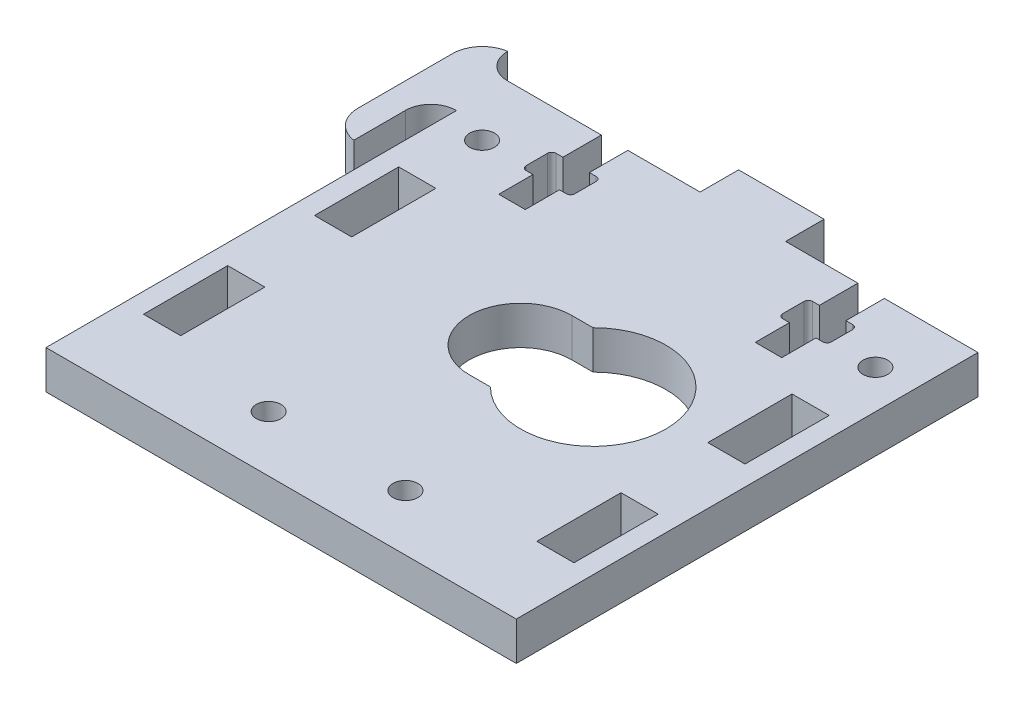
SolidWorks part; units mm, degrees
ref_plane "Front Plane" through (0, 0, 0) normal (0, 0, 1) x (1, 0, 0)
ref_plane "Top Plane" through (0, 0, 0) normal (0, 1, 0) x (1, 0, 0)
ref_plane "Right Plane" through (0, 0, 0) normal (1, 0, 0) x (0, 0, -1)
sketch "Sketch1" plane through (0, 0, 0) normal (0, 1, 0) x (1, 0, 0)
  line L1 (-27.5, 27) -> (27.5, 27)
  line L2 (-27.5, 27) -> (-27.5, -27)
  line L3 (-27.5, -27) -> (27.5, -27)
  line L4 (27.5, 27) -> (27.5, -27)
  line L5 (-27.5, 27) -> (27.5, -27) construction
  line L6 (-27.5, -27) -> (27.5, 27) construction
  point P0 (0, 0)
  dimension "D1" = 55
  dimension "D2" = 54
extrude "MainShape" add sketch "Sketch1" along normal blind 4.5
sketch "Sketch2" plane through (0, 4.5, 0) normal (0, 1, 0) x (1, 0, 0)
  line L0 (0, -27) -> (0, 27) construction
  line L1 (-27.5, -27) -> (27.5, -27) construction
  line L2 (27.5, 27) -> (-27.5, 27) construction
  line L4 (-5, 31.5) -> (5, 31.5)
  line L5 (-5, 31.5) -> (-5, 22.5)
  line L6 (-5, 22.5) -> (5, 22.5)
  line L7 (5, 31.5) -> (5, 22.5)
  line L8 (-5, 31.5) -> (5, 22.5) construction
  line L9 (-5, 22.5) -> (5, 31.5) construction
  dimension "D1" = 10
  dimension "D2" = 4.5
extrude "Tab1" add sketch "Sketch2" against normal through all
sketch "Sketch4" plane through (0, 4.5, 0) normal (0, 1, 0) x (1, 0, 0)
  line L0 (0, 31.5) -> (0, -27) construction
  line L1 (5, 31.5) -> (-5, 31.5) construction
  line L2 (-27.5, -27) -> (27.5, -27) construction
  line L3 (-15, 27) -> (-15, 15) construction
  line L4 (-5, 27) -> (-27.5, 27) construction
  line L5 (-13.45, 15) -> (-16.55, 15) construction
  line L6 (-16.55, 15) -> (-16.55, 27) construction
  line L7 (-13.45, 15) -> (-16.55, 15)
  line L8 (-16.55, 15) -> (-16.55, 19)
  line L9 (-16.55, 19) -> (-17.35, 19)
  line L10 (-17.85, 19.5) -> (-17.85, 22)
  line L11 (-17.35, 22.5) -> (-16.55, 22.5)
  line L12 (-16.55, 22.5) -> (-16.55, 27)
  line L13 (-16.55, 27) -> (-13.45, 27)
  line L14 (-13.45, 15) -> (-13.45, 27) construction
  line L15 (-13.45, 22.5) -> (-13.45, 27)
  line L16 (-12.65, 22.5) -> (-13.45, 22.5)
  line L17 (-12.15, 19.5) -> (-12.15, 22)
  line L18 (-13.45, 19) -> (-12.65, 19)
  line L19 (-13.45, 15) -> (-13.45, 19)
  line L20 (13.45, 15) -> (13.45, 27) construction
  line L21 (16.55, 15) -> (16.55, 27) construction
  line L22 (13.45, 15) -> (16.55, 15) construction
  line L23 (15, 27) -> (15, 15) construction
  line L24 (13.45, 15) -> (13.45, 19)
  line L25 (13.45, 19) -> (12.65, 19)
  line L26 (12.15, 19.5) -> (12.15, 22)
  line L27 (12.65, 22.5) -> (13.45, 22.5)
  line L28 (13.45, 22.5) -> (13.45, 27)
  line L29 (16.55, 27) -> (13.45, 27)
  line L30 (16.55, 22.5) -> (16.55, 27)
  line L31 (17.35, 22.5) -> (16.55, 22.5)
  line L32 (17.85, 19.5) -> (17.85, 22)
  line L33 (16.55, 19) -> (17.35, 19)
  line L34 (16.55, 15) -> (16.55, 19)
  line L35 (13.45, 15) -> (16.55, 15)
  arc A0 (-17.35, 19) -> (-17.85, 19.5) centre (-17.35, 19.5) cw
  arc A1 (-12.15, 19.5) -> (-12.65, 19) centre (-12.65, 19.5) cw
  arc A2 (-12.65, 22.5) -> (-12.15, 22) centre (-12.65, 22) cw
  arc A3 (-17.85, 22) -> (-17.35, 22.5) centre (-17.35, 22) cw
  arc A4 (17.85, 22) -> (17.35, 22.5) centre (17.35, 22) ccw
  arc A5 (12.65, 22.5) -> (12.15, 22) centre (12.65, 22) ccw
  arc A6 (12.15, 19.5) -> (12.65, 19) centre (12.65, 19.5) ccw
  arc A7 (17.35, 19) -> (17.85, 19.5) centre (17.35, 19.5) ccw
  point P24 (-17.85, 19)
  point P27 (-12.15, 19)
  point P30 (-12.15, 22.5)
  point P33 (-17.85, 22.5)
  point P56 (17.85, 22.5)
  point P57 (12.15, 22.5)
  point P58 (12.15, 19)
  point P59 (17.85, 19)
  dimension "D7" = 0.5
  dimension "D1" = 12
  dimension "D2" = 1.55
  dimension "D3" = 3.5
  dimension "D4" = 2.85
  dimension "D5" = 8
  dimension "D6" = 15
extrude "Cut-Extrude2" cut sketch "Sketch4" against normal through all
sketch "Sketch5" plane through (0, 4.5, 0) normal (0, 1, 0) x (1, 0, 0)
  line L0 (0, -27) -> (0, 31.5) construction
  line L1 (-27.5, -27) -> (27.5, -27) construction
  line L2 (5, 31.5) -> (-5, 31.5) construction
  line L3 (23, 27) -> (23, -27) construction
  line L4 (27.5, 27) -> (16.55, 27) construction
  line L5 (-23, 27) -> (-23, -27) construction
  line L6 (20.825, 11.925) -> (25.175, 11.925)
  line L7 (20.825, 11.925) -> (20.825, 2.075)
  line L8 (20.825, 2.075) -> (25.175, 2.075)
  line L9 (25.175, 11.925) -> (25.175, 2.075)
  line L10 (20.825, 11.925) -> (25.175, 2.075) construction
  line L11 (20.825, 2.075) -> (25.175, 11.925) construction
  line L12 (-20.825, 2.075) -> (-25.175, 11.925) construction
  line L13 (-20.825, 11.925) -> (-25.175, 2.075) construction
  line L14 (-25.175, 11.925) -> (-25.175, 2.075)
  line L15 (-20.825, 2.075) -> (-25.175, 2.075)
  line L16 (-20.825, 11.925) -> (-20.825, 2.075)
  line L17 (-20.825, 11.925) -> (-25.175, 11.925)
  line L18 (-27.5, -3) -> (27.5, -3) construction
  line L19 (-27.5, 27) -> (-27.5, -27) construction
  line L20 (27.5, -27) -> (27.5, 27) construction
  line L21 (-20.825, -17.925) -> (-25.175, -8.075) construction
  line L22 (-20.825, -8.075) -> (-25.175, -17.925) construction
  line L23 (20.825, -8.075) -> (25.175, -17.925) construction
  line L24 (20.825, -17.925) -> (25.175, -8.075) construction
  line L25 (-20.825, -17.925) -> (-25.175, -17.925)
  line L26 (-20.825, -17.925) -> (-20.825, -8.075)
  line L27 (-20.825, -8.075) -> (-25.175, -8.075)
  line L28 (-25.175, -17.925) -> (-25.175, -8.075)
  line L29 (25.175, -17.925) -> (25.175, -8.075)
  line L30 (20.825, -8.075) -> (25.175, -8.075)
  line L31 (20.825, -17.925) -> (20.825, -8.075)
  line L32 (20.825, -17.925) -> (25.175, -17.925)
  line L33 (-20.825, 11.925) -> (-25.175, 2.075) construction
  point P10 (23, 7)
  point P21 (-23, 7)
  point P36 (-23, -13)
  point P37 (23, -13)
  dimension "D1" = 23
  dimension "D2" = 9.85
  dimension "D3" = 4.35
  dimension "D4" = 20
  dimension "D5" = 20
extrude "Cut-Extrude3" cut sketch "Sketch5" against normal through all
sketch "Sketch6" plane through (0, 4.5, 0) normal (0, 1, 0) x (1, 0, 0)
  line L0 (0, -27) -> (0, 27) construction
  line L1 (5, 31.5) -> (-5, 31.5) construction
  line L3 (-27.5, 1) -> (27.5, 1) construction
  line L4 (-27.5, 27) -> (-27.5, -27) construction
  line L5 (27.5, -27) -> (27.5, 27) construction
  line L6 (27.5, 27) -> (16.55, 27) construction
  line L7 (-27.5, -27) -> (27.5, -27) construction
  line L9 (-27.5, 27) -> (27.5, 27) construction
  circle A0 centre (0, 1) radius 12
  point P4 (0, 31.5)
  dimension "D1" = 24
  dimension "D2" = 26
extrude "Cut-Extrude4" cut sketch "Sketch6" against normal through all
sketch "Sketch7" plane through (0, 4.5, 0) normal (0, 1, 0) x (1, 0, 0)
  line L0 (0, 1) -> (0, -27) construction
  line L3 (-27.5, -27) -> (27.5, -27) construction
  line L4 (8, -20.46) -> (-8, -20.46) construction
  circle A1 centre (-8, -20.46) radius 1.45
  circle A2 centre (8, -20.46) radius 1.45
  point P8 (0, -20.46)
  dimension "D1" = 2.9
  dimension "D3" = 21.46
extrude "Cut-Extrude5" [suppressed] cut sketch "Sketch7" against normal through all
sketch "Sketch8" plane through (0, 4.5, 0) normal (0, 1, 0) x (1, 0, 0)
  line L0 (-12, 1) -> (12, 1) construction
  line L1 (0, 1) -> (0, -20.46) construction
  line L2 (8, -20.46) -> (-8, -20.46) construction
  line L3 (0, -11) -> (0, 13) construction
  circle A0 centre (-8, -20.46) radius 1.45
  circle A1 centre (0, 1) radius 12 construction
  circle A2 centre (8, -20.46) radius 1.45
  dimension "D3" = 2.9
  dimension "D1" = 90
  dimension "D4" = 21.46
extrude "Cut-Extrude6" cut sketch "Sketch8" against normal through all
sketch "Sketch9" plane through (0, 4.5, 0) normal (0, 1, 0) x (1, 0, 0)
  line L0 (0, -27) -> (0, 31.5) construction
  line L1 (-27.5, -27) -> (27.5, -27) construction
  line L2 (5, 31.5) -> (-5, 31.5) construction
  line L3 (16, -27) -> (16, -16) construction
  line L4 (14.45, -16) -> (17.55, -16) construction
  line L5 (17.55, -16) -> (17.55, -27) construction
  line L6 (17.55, -27) -> (17.55, -22.5)
  line L7 (17.55, -22.5) -> (18.35, -22.5)
  line L8 (18.85, -22) -> (18.85, -19.5)
  line L9 (18.35, -19) -> (17.55, -19)
  line L10 (17.55, -19) -> (17.55, -16)
  line L11 (17.55, -16) -> (14.45, -16)
  line L12 (17.55, -27) -> (14.45, -27)
  line L13 (14.45, -16) -> (14.45, -27) construction
  line L14 (14.45, -19) -> (14.45, -16)
  line L15 (13.65, -19) -> (14.45, -19)
  line L16 (13.15, -22) -> (13.15, -19.5)
  line L17 (14.45, -22.5) -> (13.65, -22.5)
  line L18 (14.45, -27) -> (14.45, -22.5)
  line L19 (-14.45, -16) -> (-14.45, -27) construction
  line L20 (-17.55, -16) -> (-17.55, -27) construction
  line L21 (-14.45, -16) -> (-17.55, -16) construction
  line L22 (-16, -27) -> (-16, -16) construction
  line L23 (-14.45, -27) -> (-14.45, -22.5)
  line L24 (-14.45, -22.5) -> (-13.65, -22.5)
  line L25 (-13.15, -22) -> (-13.15, -19.5)
  line L26 (-13.65, -19) -> (-14.45, -19)
  line L27 (-14.45, -19) -> (-14.45, -16)
  line L28 (-17.55, -27) -> (-14.45, -27)
  line L29 (-17.55, -16) -> (-14.45, -16)
  line L30 (-17.55, -19) -> (-17.55, -16)
  line L31 (-18.35, -19) -> (-17.55, -19)
  line L32 (-18.85, -22) -> (-18.85, -19.5)
  line L33 (-17.55, -22.5) -> (-18.35, -22.5)
  line L34 (-17.55, -27) -> (-17.55, -22.5)
  arc A0 (18.35, -22.5) -> (18.85, -22) centre (18.35, -22) ccw
  arc A1 (18.85, -19.5) -> (18.35, -19) centre (18.35, -19.5) ccw
  arc A2 (13.15, -19.5) -> (13.65, -19) centre (13.65, -19.5) cw
  arc A3 (13.65, -22.5) -> (13.15, -22) centre (13.65, -22) cw
  arc A4 (-13.65, -22.5) -> (-13.15, -22) centre (-13.65, -22) ccw
  arc A5 (-13.15, -19.5) -> (-13.65, -19) centre (-13.65, -19.5) ccw
  arc A6 (-18.85, -19.5) -> (-18.35, -19) centre (-18.35, -19.5) cw
  arc A7 (-18.35, -22.5) -> (-18.85, -22) centre (-18.35, -22) cw
  point P16 (18.85, -22.5)
  point P19 (18.85, -19)
  point P30 (13.15, -19)
  point P31 (13.15, -22.5)
  point P54 (-13.15, -22.5)
  point P55 (-13.15, -19)
  point P56 (-18.85, -19)
  point P57 (-18.85, -22.5)
  dimension "D7" = 0.5
  dimension "D2" = 1.55
  dimension "D1" = 11
  dimension "D3" = 8
  dimension "D4" = 3.5
  dimension "D5" = 2.85
  dimension "D6" = 16
extrude "Cut-Extrude7" [suppressed] cut sketch "Sketch9" against normal through all
sketch "Sketch10" [suppressed] plane through (0, 0, 27) normal (0, 0, 1) x (1, 0, 0)
  line L0 (-27.5, 2.25) -> (27.5, 2.25) construction
  line L1 (-27.5, 4.5) -> (-27.5, 0) construction
  line L2 (27.5, 4.5) -> (27.5, 0) construction
  line L3 (-16, 4.5) -> (-16, 0) construction
  line L4 (-14.25, 4.5) -> (-17.75, 4.5) construction
  line L5 (16, 4.5) -> (16, 0) construction
  line L6 (17.75, 4.5) -> (14.25, 4.5) construction
  line L7 (17.75, 0) -> (14.25, 0) construction
  line L8 (-14.25, 0) -> (-17.75, 0) construction
  circle A0 centre (-16, 2.25) radius 1.6
  circle A1 centre (16, 2.25) radius 1.6
  dimension "D1" = 3.2
  dimension "D2" = 3.2
sketch "Sketch11" plane through (0, 4.5, 0) normal (0, 1, 0) x (1, 0, 0)
  line L0 (-20.825, 7) -> (-25.175, 7) construction
  line L1 (-20.825, 2.075) -> (-20.825, 11.925) construction
  line L2 (-25.175, 11.925) -> (-25.175, 2.075) construction
  line L3 (-23, 7) -> (-23, 27) construction
  line L4 (-16.55, 27) -> (-27.5, 27) construction
  line L5 (0, 31.5) -> (0, 0) construction
  line L6 (5, 31.5) -> (-5, 31.5) construction
  line L7 (23, 7) -> (23, 27) construction
  line L8 (20.825, 7) -> (25.175, 7) construction
  line L9 (-23, 7) -> (-23, 27) construction
  circle A0 centre (-23, 19.5) radius 1.45
  circle A1 centre (23, 19.5) radius 1.45
  dimension "D1" = 2.9
  dimension "D2" = 7.5
extrude "Cut-Extrude8" cut sketch "Sketch11" against normal through all
sketch "Sketch12" [suppressed] plane through (0, 4.5, 0) normal (0, 1, 0) x (1, 0, 0)
  line L0 (-27.5, -7) -> (-34, -17)
  line L1 (-27.5, 27) -> (-27.5, -27) construction
  line L2 (-34, -17) -> (-34, -27)
  line L3 (-34, -27) -> (-27.5, -27)
  line L4 (-27.5, -27) -> (-27.5, -7)
  line L5 (-27.5, -27) -> (27.5, -27) construction
  line L6 (0, -27) -> (0, 31.5) construction
  line L7 (5, 31.5) -> (-5, 31.5) construction
  line L8 (27.5, -27) -> (27.5, -7)
  line L9 (34, -27) -> (27.5, -27)
  line L10 (34, -17) -> (34, -27)
  line L11 (27.5, -7) -> (34, -17)
  point P4 (0, -27)
  dimension "D1" = 34
  dimension "D2" = 10
  dimension "D3" = 20
extrude "Boss-Extrude1" [suppressed] add sketch "Sketch12" against normal through all
sketch "Sketch14" [suppressed] plane through (0, 4.5, 0) normal (0, 1, 0) x (1, 0, 0)
  line L0 (-34, -27) -> (34, -27) construction
  line L2 (-34, -27) -> (34, -27) construction
  line L3 (0, -27) -> (0, 31.5) construction
  line L4 (5, 31.5) -> (-5, 31.5) construction
  line L6 (26.25, -16.5) -> (26.25, -27) construction
  line L8 (-28, -27) -> (-28, -16.5) construction
  line L9 (-26.25, -16.5) -> (-29.75, -16.5) construction
  line L10 (-29.75, -16.5) -> (-29.75, -27) construction
  line L11 (-26.25, -27) -> (-29.75, -27)
  line L12 (-29.75, -27) -> (-29.75, -23.2)
  line L13 (-29.75, -23.2) -> (-30.75, -23.2)
  line L14 (-31, -22.95) -> (-31, -19.25)
  line L15 (-30.75, -19) -> (-29.75, -19)
  line L16 (-29.75, -19) -> (-29.75, -16.5)
  line L17 (-29.75, -16.5) -> (-26.25, -16.5)
  line L18 (-26.25, -16.5) -> (-26.25, -27) construction
  line L19 (-26.25, -19) -> (-26.25, -16.5)
  line L20 (-25.25, -19) -> (-26.25, -19)
  line L21 (-25, -22.95) -> (-25, -19.25)
  line L22 (-26.25, -23.2) -> (-25.25, -23.2)
  line L23 (-26.25, -27) -> (-26.25, -23.2)
  line L24 (29.75, -16.5) -> (29.75, -27) construction
  line L25 (26.25, -16.5) -> (29.75, -16.5) construction
  line L26 (28, -27) -> (28, -16.5) construction
  line L27 (26.25, -27) -> (26.25, -23.2)
  line L28 (26.25, -23.2) -> (25.25, -23.2)
  line L29 (25, -22.95) -> (25, -19.25)
  line L30 (25.25, -19) -> (26.25, -19)
  line L31 (26.25, -19) -> (26.25, -16.5)
  line L32 (29.75, -16.5) -> (26.25, -16.5)
  line L33 (29.75, -19) -> (29.75, -16.5)
  line L34 (30.75, -19) -> (29.75, -19)
  line L35 (31, -22.95) -> (31, -19.25)
  line L36 (29.75, -23.2) -> (30.75, -23.2)
  line L37 (29.75, -27) -> (29.75, -23.2)
  line L38 (26.25, -27) -> (29.75, -27)
  line L39 (-26.25, -16.5) -> (-26.25, -27) construction
  arc A0 (-30.75, -23.2) -> (-31, -22.95) centre (-30.75, -22.95) cw
  arc A1 (-31, -19.25) -> (-30.75, -19) centre (-30.75, -19.25) cw
  arc A2 (-25, -19.25) -> (-25.25, -19) centre (-25.25, -19.25) ccw
  arc A3 (-25.25, -23.2) -> (-25, -22.95) centre (-25.25, -22.95) ccw
  arc A4 (25.25, -23.2) -> (25, -22.95) centre (25.25, -22.95) cw
  arc A5 (25, -19.25) -> (25.25, -19) centre (25.25, -19.25) cw
  arc A6 (31, -19.25) -> (30.75, -19) centre (30.75, -19.25) ccw
  arc A7 (30.75, -23.2) -> (31, -22.95) centre (30.75, -22.95) ccw
  point P2 (0, -27)
  dimension "D10" = 0.5
  dimension "D4" = 1.55
  dimension "D6" = 11
  dimension "D2" = 28
  dimension "D3" = 2.85
  dimension "D5" = 3.5
  dimension "D7" = 8
extrude "Cut-Extrude9" [suppressed] cut sketch "Sketch14" against normal through all
sketch "Sketch15" plane through (0, 4.5, 0) normal (0, 1, 0) x (1, 0, 0)
  circle A0 centre (0, 1) radius 12
  circle A1 centre (0, 1) radius 6
  circle A2 centre (0, 1) radius 12 construction
  dimension "D1" = 12
extrude "Boss-Extrude2" add sketch "Sketch15" against normal through all
sketch "Sketch16" plane through (0, 4.5, 0) normal (0, 1, 0) x (1, 0, 0)
  line L0 (0, 1) -> (27.5, 1) construction
  line L1 (27.5, -27) -> (27.5, 27) construction
  line L2 (0, 7) -> (2.4792, 7)
  line L3 (0, -5) -> (2.4792, -5)
  line L4 (0, 7) -> (0, -5)
  arc A0 (2.4792, -5) -> (2.4792, 7) centre (8.5, 1) ccw
  circle A1 centre (0, 1) radius 6 construction
  dimension "D1" = 17
  dimension "D2" = 8.5
extrude "Cut-Extrude10" cut sketch "Sketch16" against normal through all
sketch "Sketch17" plane through (0, 4.5, 0) normal (0, 1, 0) x (1, 0, 0)
  line L0 (-27.5, 22) -> (-27.5, 18) construction
  line L1 (-27.5, 27) -> (-27.5, -27) construction
  line L2 (-27.5, 25.5) -> (-27.5, 23.5)
  line L3 (-29, 22) -> (-29, 18)
  line L4 (-27.5, 22) -> (-27.5, 18) construction
  line L5 (-27.5, 16.5) -> (-27.5, 14.5)
  line L6 (-31, 22) -> (-31, 18)
  line L7 (-27.5, 25.5) -> (-27.5, 14.5) construction
  arc A0 (-27.5, 23.5) -> (-29, 22) centre (-27.5, 22) ccw
  arc A1 (-29, 18) -> (-27.5, 16.5) centre (-27.5, 18) ccw
  arc A2 (-27.5, 25.5) -> (-31, 22) centre (-27.5, 22) ccw
  arc A3 (-31, 18) -> (-27.5, 14.5) centre (-27.5, 18) ccw
  point P10 (-27.5, 20)
  dimension "D1" = 1.5
  dimension "D2" = 1.5
  dimension "D3" = 2
  dimension "D4" = 4
  dimension "D5" = 20
  dimension "D7" = 2
extrude "CableTieSlot" [suppressed] add sketch "Sketch17" against normal through all
sketch "Sketch18" plane through (0, 4.5, 0) normal (0, 1, 0) x (1, 0, 0)
  line L0 (-27.5, 27) -> (-27.55, 27)
  line L1 (-33.5, 30) -> (-33.5, 12)
  line L2 (-33.5, 12) -> (-30.5, 12)
  line L3 (-30.5, 12) -> (-30.5, 18.05)
  line L4 (-27.55, 21) -> (-27.5, 21)
  line L5 (-27.5, 27) -> (-27.5, -27) construction
  line L6 (-27.5, 21) -> (-27.5, 27)
  line L7 (-16.55, 27) -> (-27.5, 27) construction
  line L8 (-33.5, 30) -> (-30.5, 30)
  line L9 (-30.5, 30) -> (-30.5, 29.95)
  arc A0 (-27.55, 27) -> (-30.5, 29.95) centre (-27.55, 29.95) cw
  arc A1 (-30.5, 18.05) -> (-27.55, 21) centre (-27.55, 18.05) cw
  point P17 (-30.5, 27)
  dimension "D1" = 2.95
  dimension "D2" = 2.95
  dimension "D3" = 6
  dimension "D4" = 3
  dimension "D5" = 15
  dimension "D6" = 3
  dimension "D7" = 3
extrude "Boss-Extrude3" add sketch "Sketch18" against normal through all
fillet "Fillet1" radius 3.5 2 edges at (-33.5, 2.25, -30) (-33.5, 2.25, -12)
equation "\"X-ROD-SPACING\"=45"
equation "\"Y-ROD-SPACING\"=75"
equation "\"Z-ROD-SPACING\"=17.5"
equation "\"Y-BED-OFFSET\"=2"
equation "\"Y-BED-ROD-INSET\"=3.5"
equation "\"Y-BED-SCREW-SPACING\"=209"
equation "\"Y-BED-SCREW-CUTOUT-SLOT-HEIGHT\"=2"
equation "\"T-SLOT-NUT-FILLET-RADIUS\"=0.5"
equation "\"T-SLOT-SCREW-SHAFT-RADIUS\"=1.55"
equation "\"T-SLOT-SCREW-SHAFT-CUTOUT-LENGTH\"=11"
equation "\"T-SLOT-NUT-DEPTH\"=3.5"
equation "\"T-SLOT-NUT-WIDTH\"=2.85"
equation "\"T-SLOT-NUT-END-DISTANCE\"=8"
equation "\"ACRYLIC-THICKNESS\"=10"
equation "\"ACRYLIC-THICKNESS2\"=4.5"
equation "\"ACRYLIC-TAB-CUTOUT-SIZE\"=\"ACRYLIC-THICKNESS\"+\"ACRYLIC-TAB-TOLERANCE\"*2"
equation "\"ACRYLIC-TAB-WIDTH\"=\"ACRYLIC-THICKNESS\""
equation "\"ACRYLIC-M3-HOLE\"=2.9"
equation "\"SMOOTHROD-CAP-SCREW-DISTANCE\"=20"
equation "\"FRAME-WIDTH-INNER\"=370"
equation "\"NEMA17-HOLE-SPACING\"=31"
equation "\"NEMA17-CENTRAL-CUTOUT\"=22.5"
equation "\"Z-BRACKET-REACH\"=55"
equation "\"Z-ROD-INSET\"=13.5"
equation "\"TOP-BRACKET-SPACING\"=40"
equation "\"SMOOTHROD-X-LENGTH\"=350"
equation "\"SMOOTHROD-Y-LENGTH\"=350"
equation "\"SMOOTHROD-Z-LENGTH\"=350"
equation "\"SMOOTHROD-TIGHTENING-HEADROOM\"=.25"
equation "\"LEADSCREW-Z-LENGTH\"=300"
equation "\"SCREW-LENGTH-FRAME\"=\"ACRYLIC-THICKNESS\" + 10"
equation "\"SCREW-LENGTH-MOTOR\"=\"ACRYLIC-THICKNESS\" + 5"
equation "\"SCREW-LENGTH-EXTRUDER\"=28"
equation "\"SCREW-HEAD-RADIUS\"=6"
equation "\"PRINTED-X-SMOOTHROD-DIAMETER\"=8.8"
equation "\"PRINTED-X-SMOOTHROD-CUTOUT\"=10"
equation "\"PRINTED-X-BASE-HEIGHT\"=10"
equation "\"PRINTED-LM8UU-CUTOUT-SIZE\"=15.5"
equation "\"PRINTED-LM8UU-CUTOUT-LENGTH\"=24.5"
equation "\"PRINTED-X-IDLER-HEIGHT\"=16"
equation "\"PSU-MOUNTING-WIDTH\"=95"
equation "\"PSU-MOUNTING-HEIGHT\"=177"
equation "\"Y-BELT-TO-ROD-DISTANCE\"=20"
equation "\"SPOOL-HOLDER-ROD-SPACING\"=150"
equation "\"ACRYLIC-X-CARRIAGE-WIDTH\"=55"
equation "\"ACRYLIC-X-CARRIAGE-HEIGHT\"=75"
equation "\"ACRYLIC-X-CARRIAGE-SCREW-SPACING-X\"=15"
equation "\"ACRYLIC-X-CARRIAGE-SCREW-SPACING-Y\"=33"
equation "\"ACRYLIC-X-CARRIAGE-CENTER-TAB-SPACING\"=14"
equation "\"D1@Sketch1\"=\"ACRYLIC-X-CARRIAGE-WIDTH\""
equation "\"D1@MainShape\" = \"ACRYLIC-THICKNESS2\""
equation "\"D1@Sketch2\"=\"ACRYLIC-TAB-WIDTH\""
equation "\"D2@Sketch2\"=\"ACRYLIC-THICKNESS2\""
equation "\"D1@Sketch4\"=\"T-SLOT-SCREW-SHAFT-CUTOUT-LENGTH\"+1"
equation "\"D2@Sketch4\"=\"T-SLOT-SCREW-SHAFT-RADIUS\""
equation "\"D3@Sketch4\"=\"T-SLOT-NUT-DEPTH\""
equation "\"D4@Sketch4\"=\"T-SLOT-NUT-WIDTH\""
equation "\"D5@Sketch4\"=\"T-SLOT-NUT-END-DISTANCE\""
equation "\"D6@Sketch4\"=\"ACRYLIC-X-CARRIAGE-SCREW-SPACING-X\""
equation "\"D7@Sketch4\"=\"T-SLOT-NUT-FILLET-RADIUS\""
equation "\"ACRYLIC-X-CARRIAGE-EXTRUDER-SHELF-DEPTH\"=\"ACRYLIC-X-CARRIAGE-EXTRUDER-OFFSET\" + 28"
equation "\"D2@Sketch1\"=\"ACRYLIC-X-CARRIAGE-EXTRUDER-SHELF-DEPTH\""
equation "\"ACRYLIC-X-CARRIAGE-LM8UU-CUTOUT-WIDTH\"=24.25"
equation "\"ACRYLIC-X-CARRIAGE-EXTRUDER-BRACE-SPACING\"=23"
equation "\"ACRYLIC-X-CARRIAGE-EXTRUDER-BRACE-TAB-OFFSET\"=20"
equation "\"ACRYLIC-X-CARRIAGE-EXTRUDER-BRACE-HEIGHT\"=35"
equation "\"ACRYLIC-X-CARRIAGE-EXTRUDER-BRACE-SCREW-SPACING\"=22"
equation "\"D1@Sketch5\"=\"ACRYLIC-X-CARRIAGE-EXTRUDER-BRACE-SPACING\""
equation "\"D2@Sketch5\"=\"ACRYLIC-TAB-WIDTH\"-\"KERF\"*2"
equation "\"D3@Sketch5\"=\"ACRYLIC-THICKNESS2\"-\"KERF\"*2"
equation "\"D4@Sketch5\"=\"ACRYLIC-X-CARRIAGE-EXTRUDER-BRACE-TAB-OFFSET\""
equation "\"D1@Sketch7\"=\"ACRYLIC-M3-HOLE\""
equation "\"D3@Sketch8\"=\"ACRYLIC-M3-HOLE\""
equation "\"ACRYLIC-X-CARRIAGE-EXTRUDER-ANGLE\"=90"
equation "\"D1@Sketch8\"=\"ACRYLIC-X-CARRIAGE-EXTRUDER-ANGLE\""
equation "\"ACRYLIC-X-CARRIAGE-EXTRUDER-OFFSET\"=26"
equation "\"D2@Sketch6\"=\"ACRYLIC-X-CARRIAGE-EXTRUDER-OFFSET\""
equation "\"D1@Sketch9\"=\"T-SLOT-SCREW-SHAFT-CUTOUT-LENGTH\""
equation "\"D2@Sketch9\"=\"T-SLOT-SCREW-SHAFT-RADIUS\""
equation "\"D3@Sketch9\"=\"T-SLOT-NUT-END-DISTANCE\""
equation "\"D4@Sketch9\"=\"T-SLOT-NUT-DEPTH\""
equation "\"D5@Sketch9\"=\"T-SLOT-NUT-WIDTH\""
equation "\"D7@Sketch9\"=\"T-SLOT-NUT-FILLET-RADIUS\""
equation "\"ACRYLIC-TAB-TOLERANCE\"=-.05"
equation "\"D1@Sketch11\"=\"ACRYLIC-M3-HOLE\""
equation "\"D6@Sketch14\"=\"T-SLOT-SCREW-SHAFT-CUTOUT-LENGTH\""
equation "\"D3@Sketch14\"=\"T-SLOT-NUT-WIDTH\""
equation "\"D5@Sketch14\"=\"T-SLOT-NUT-DEPTH\""
equation "\"D4@Sketch14\"=\"T-SLOT-SCREW-SHAFT-RADIUS\""
equation "\"D10@Sketch14\"=\"T-SLOT-NUT-FILLET-RADIUS\""
equation "\"D7@Sketch14\"=\"T-SLOT-NUT-END-DISTANCE\""
equation "\"KERF\"=0.075"
equation "\"PRINTED-M3-HOLE\"=3.5"
equation "\"PRINTED-M3-NUT-AF\"=6.25"
equation "\"ACRYLIC-X-CARRIAGE-LM8UU-CUTOUT-HEIGHT\"=11.0"
equation "\"ACRYLIC-X-CARRIAGE-DUAL-WIDTH-MULTIPLIER\"=1.65"
equation "\"ACRYLIC-X-CARRIAGE-DUAL-HOTEND-SPACING\"=42"
equation "\"ACRYLIC-X-CARRIAGE-DUAL-WIDTH\"=75"
equation "\"ACRYLIC-X-CARRIAGE-DUAL-FAN-OFFSET\"=52"
equation "\"ACRYLIC-X-CARRIAGE-DUAL-FAN-HEIGHT\"=20"
equation "\"ACRYLIC-X-CARRIAGE-DUAL-HOTEND-SEPARATION\"=36"
equation "\"ACRYLIC-X-CARRIAGE-DUAL-MOUNT-PLATE-DEPTH\"=75"
equation "\"ACRYLIC-X-CARRIAGE-DUAL-MOUNT-BRACE-WIDTH\"=33"
equation "\"ACRYLIC-X-CARRIAGE-DUAL-MOUNT-SCREW-WIDTH\"=40"
equation "\"BLOWER-FAN-WIDTH\"=15"
